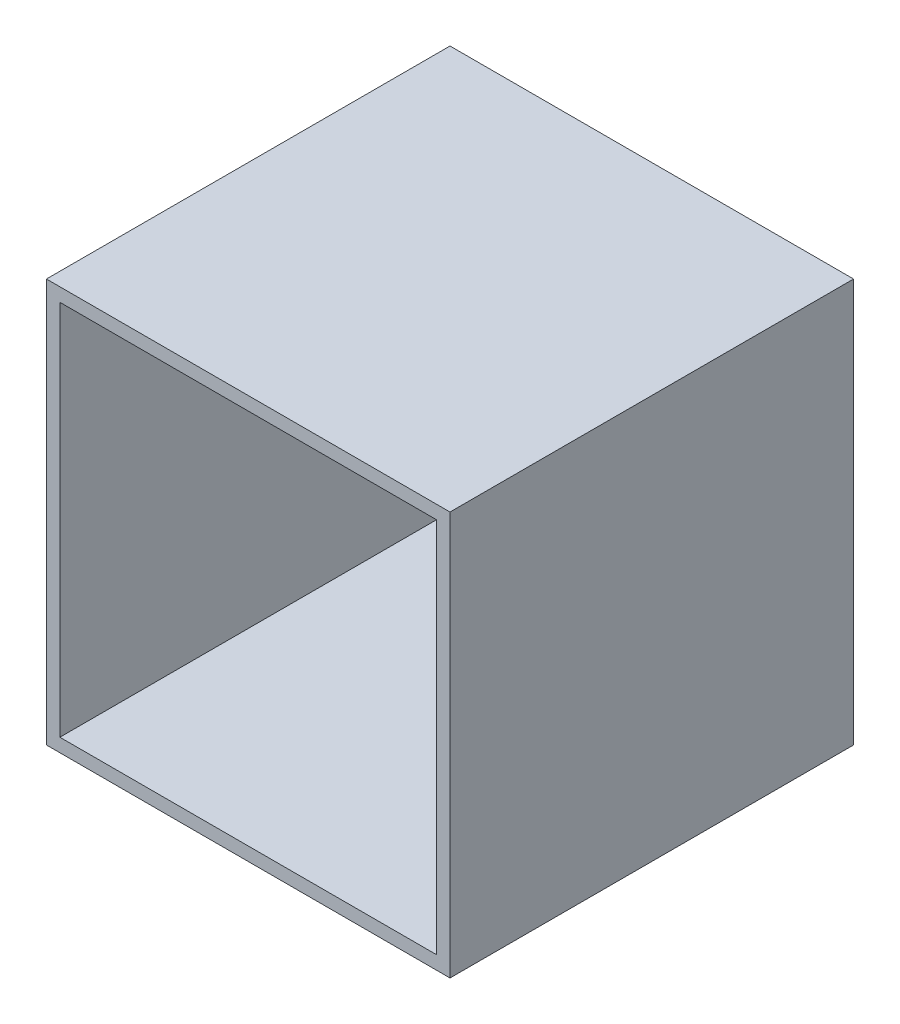
SolidWorks part; units mm, degrees
ref_plane "Front Plane" through (0, 0, 0) normal (0, 0, 1) x (1, 0, 0)
ref_plane "Top Plane" through (0, 0, 0) normal (0, 1, 0) x (1, 0, 0)
ref_plane "Right Plane" through (0, 0, 0) normal (1, 0, 0) x (0, 0, -1)
sketch "Sketch1" plane through (0, 0, 0) normal (0, 1, 0) x (1, 0, 0)
  line L1 (-38.1, -38.1) -> (38.1, -38.1)
  line L2 (-38.1, -38.1) -> (-38.1, 38.1)
  line L3 (-38.1, 38.1) -> (38.1, 38.1)
  line L4 (38.1, -38.1) -> (38.1, 38.1)
  line L5 (-38.1, -38.1) -> (38.1, 38.1) construction
  line L6 (-38.1, 38.1) -> (38.1, -38.1) construction
  point P0 (0, 0)
  dimension "D1" = 76.2
  dimension "D2" = 76.2
extrude "box" add sketch "Sketch1" along normal blind 76.2
shell "hollow it" thickness 2.54 removed face at (0, 38.1, 38.1)
sketch "Sketch2" plane through (0, 0, -38.1) normal (0, 0, -1) x (-1, 0, 0)
  line L0 (-38.1, 76.2) -> (38.1, 76.2) construction
  line L1 (-31.75, 69.85) -> (-24.13, 69.85)
  line L2 (-31.75, 69.85) -> (-31.75, 6.35)
  line L3 (-31.75, 6.35) -> (-24.13, 6.35)
  line L4 (-24.13, 69.85) -> (-24.13, 6.35)
  line L6 (-38.1, 76.2) -> (-38.1, 0) construction
  dimension "D1" = 7.62
  dimension "D2" = 63.5
  dimension "D3" = 6.35
  dimension "D4" = 6.35
extrude "slider track" cut sketch "Sketch2" against normal up to surface (2.54 mm away) up to face at (0, 38.1, -35.56)
sketch "Sketch4" plane through (0, 0, -38.1) normal (0, 0, -1) x (-1, 0, 0)
  line L0 (-38.1, 76.2) -> (38.1, 76.2) construction
  circle A0 centre (0, 63.5) radius 6.35
  dimension "D1" = 12.7
  dimension "D2" = 12.7
extrude "button large ring" cut sketch "Sketch4" against normal blind 1.27
sketch "Sketch5" plane through (0, 0, -36.83) normal (0, 0, -1) x (-1, 0, 0)
  circle A0 centre (0, 63.5) radius 3.556
  circle A1 centre (0, 63.5) radius 6.35 construction
  dimension "D2" = 7.112
  dimension "D1" = 0
extrude "button small hole" cut sketch "Sketch5" against normal blind 1.27
sketch "Sketch6" plane through (0, 0, -38.1) normal (0, 0, -1) x (-1, 0, 0)
  line L0 (-3.2977, 45.72) -> (-3.2977, 52.07)
  line L1 (-3.2977, 52.07) -> (3.0523, 52.07)
  line L2 (3.0523, 52.07) -> (3.0523, 45.72)
  line L3 (3.0523, 45.72) -> (9.4023, 45.72)
  line L4 (9.4023, 45.72) -> (9.4023, 39.37)
  line L5 (9.4023, 39.37) -> (3.0523, 39.37)
  line L6 (3.0523, 39.37) -> (3.0523, 33.02)
  line L7 (3.0523, 33.02) -> (-3.2977, 33.02)
  line L8 (-3.2977, 33.02) -> (-3.2977, 39.37)
  line L9 (-3.2977, 39.37) -> (-9.6477, 39.37)
  line L10 (-9.6477, 39.37) -> (-9.6477, 45.72)
  line L11 (-9.6477, 45.72) -> (-3.2977, 45.72)
  line L12 (-38.1, 0) -> (38.1, 0) construction
  dimension "D1" = 6.35
  dimension "D2" = 6.35
  dimension "D3" = 6.35
  dimension "D4" = 6.35
  dimension "D5" = 6.35
  dimension "D6" = 6.35
  dimension "D7" = 6.35
  dimension "D8" = 6.35
  dimension "D9" = 6.35
  dimension "D10" = 33.02
extrude "dpad large shape" cut sketch "Sketch6" against normal blind 1.27
sketch "Sketch7" plane through (0, 0, -36.83) normal (0, 0, -1) x (-1, 0, 0)
  line L0 (-3.2977, 45.72) -> (-9.6477, 45.72) construction
  line L1 (-9.6477, 45.72) -> (-9.6477, 39.37) construction
  line L2 (3.0523, 33.02) -> (3.0523, 39.37) construction
  line L3 (-3.2977, 33.02) -> (3.0523, 33.02) construction
  line L4 (3.0523, 39.37) -> (9.4023, 39.37) construction
  line L5 (9.4023, 39.37) -> (9.4023, 45.72) construction
  line L6 (3.0523, 45.72) -> (3.0523, 52.07) construction
  line L7 (-3.2977, 52.07) -> (-3.2977, 45.72) construction
  line L8 (3.0523, 52.07) -> (-3.2977, 52.07) construction
  circle A0 centre (-0.1227, 48.895) radius 1.651
  circle A1 centre (6.2273, 42.672) radius 1.397
  circle A2 centre (-0.1227, 36.195) radius 1.651
  circle A3 centre (-6.4727, 42.545) radius 1.651
  point P12 (3.0523, 36.195)
  point P17 (6.2273, 39.37)
  dimension "D3" = 3.302
  dimension "D6" = 3.302
  dimension "D9" = 2.794
  dimension "D13" = 3.302
  dimension "D1" = 3.175
  dimension "D2" = 3.175
  dimension "D4" = 3.175
  dimension "D5" = 3.175
  dimension "D7" = 3.302
  dimension "D8" = 3.175
  dimension "D10" = 3.175
  dimension "D11" = 3.175
  dimension "D12" = 3.175
extrude "dpad tiny holes" cut sketch "Sketch7" against normal blind 1.27
sketch "Sketch8" plane through (0, 0, -38.1) normal (0, 0, -1) x (-1, 0, 0)
  line L0 (38.1, 76.2) -> (38.1, 0) construction
  line L1 (-38.1, 76.2) -> (38.1, 76.2) construction
  circle A0 centre (20.32, 19.05) radius 12.7
  dimension "D1" = 25.4
  dimension "D2" = 17.78
  dimension "D3" = 57.15
extrude "dial large ring" cut sketch "Sketch8" against normal blind 1.27
ref_point "dial center"
sketch "Sketch9" plane through (0, 0, -36.83) normal (0, 0, -1) x (-1, 0, 0)
  circle A0 centre (20.32, 19.05) radius 5.08
  dimension "D1" = 10.16
extrude "dial small hole" cut sketch "Sketch9" against normal blind 1.27
sketch "Sketch10" plane through (0, 73.66, 0) normal (0, -1, 0) x (1, 0, 0)
  line L0 (35.56, -35.56) -> (-35.56, -35.56) construction
  line L1 (-35.56, -35.56) -> (-35.56, 38.1) construction
  circle A0 centre (-12.7, -13.563) radius 3.81
  point P2 (0, -35.56)
  dimension "D1" = 25.4
  dimension "D2" = 22.86
extrude "obstruction for baton" add sketch "Sketch10" along normal blind 12.7
sketch "Sketch12" plane through (0, 0, -38.1) normal (0, 0, -1) x (-1, 0, 0)
  line L0 (38.1, 76.2) -> (38.1, 0) construction
  line L1 (-11.43, 30.48) -> (-2.54, 30.48)
  line L2 (-11.43, 30.48) -> (-11.43, 5.08)
  line L3 (-11.43, 5.08) -> (-2.54, 5.08)
  line L4 (-2.54, 30.48) -> (-2.54, 5.08)
  line L5 (-38.1, 0) -> (38.1, 0) construction
  dimension "D1" = 25.4
  dimension "D2" = 8.89
  dimension "D3" = 40.64
  dimension "D4" = 5.08
extrude "hole for scroll wheel" cut sketch "Sketch12" against normal blind 2.54
sketch "Sketch14" plane through (2.54, 0, 0) normal (1, 0, 0) x (0, 0, -1)
  line L0 (38.1, 5.08) -> (38.1, 30.48) construction
  circle A0 centre (38.1, 17.78) radius 6.35
extrude "nibble base 1" add sketch "Sketch14" against normal blind 5.08
sketch "Sketch15" plane through (11.43, 0, 0) normal (-1, 0, 0) x (0, 0, 1)
  line L0 (-38.1, 30.48) -> (-38.1, 5.08) construction
  circle A0 centre (-38.1, 17.78) radius 6.35
extrude "nibble base 2" add sketch "Sketch15" against normal blind 5.08
sketch "Sketch16" plane through (11.43, 0, 0) normal (-1, 0, 0) x (0, 0, 1)
  circle A0 centre (-38.1, 17.78) radius 3.302
extrude "nibble holes" cut sketch "Sketch16" against normal up to surface and the other way up to surface up to face at (16.51, 17.78, -41.275) other way up to face at (-2.54, 17.78, -41.275)
